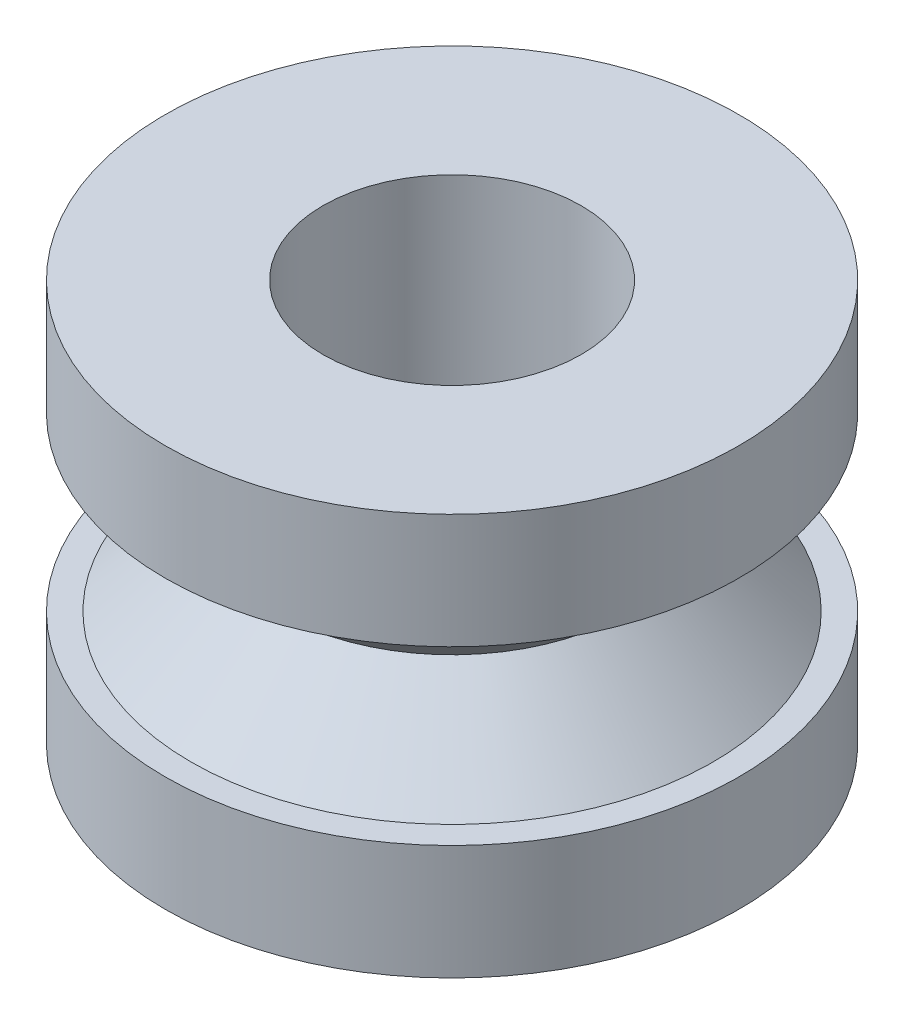
SolidWorks part; units mm, degrees
ref_plane "Спереди" through (0, 0, 0) normal (0, 0, 1) x (1, 0, 0)
ref_plane "Сверху" through (0, 0, 0) normal (0, 1, 0) x (1, 0, 0)
ref_plane "Справа" through (0, 0, 0) normal (1, 0, 0) x (0, 0, -1)
sketch "Эскиз1" plane through (0, 0, 0) normal (0, 1, 0) x (1, 0, 0)
  circle A0 centre (0, 0) radius 2.25
extrude "Вытянуть-Тонкостенный1" add sketch "Эскиз1" along normal blind 7 thin thin type one direction wall 0.8
sketch "Эскиз2" plane through (0, 0, 0) normal (0, 1, 0) x (1, 0, 0)
  circle A0 centre (0, 0) radius 5
extrude "Вытянуть-Тонкостенный2" add sketch "Эскиз2" along normal blind 2 thin thin type one direction reverse wall 2.75
sketch "Эскиз3" plane through (0, 7, 0) normal (0, 1, 0) x (1, 0, 0)
  circle A0 centre (0, 0) radius 5
extrude "Вытянуть-Тонкостенный3" add sketch "Эскиз3" against normal blind 2 thin thin type one direction reverse wall 2.75
chamfer "Фаска1" distance 1.5 angle 45 2 edges at (0, 5, 3.05) (0, 2, 3.05)
